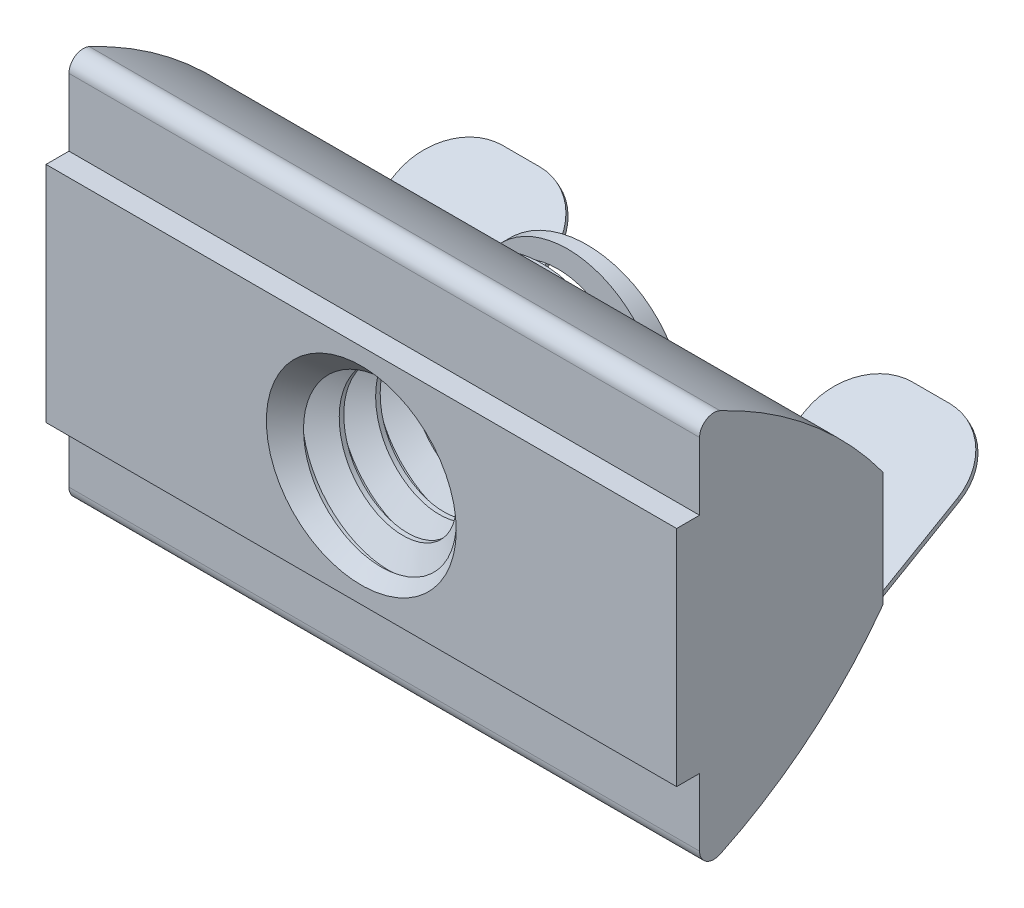
SolidWorks part; units mm, degrees
ref_plane "Front Plane" through (0, 0, 0) normal (0, 0, 1) x (1, 0, 0)
ref_plane "Top Plane" through (0, 0, 0) normal (0, 1, 0) x (1, 0, 0)
ref_plane "Right Plane" through (0, 0, 0) normal (1, 0, 0) x (0, 0, -1)
sketch "Sketch1" plane through (0, 0, 0) normal (0, 0, 1) x (1, 0, 0)
  line L1 (-11, 6.75) -> (11, 6.75)
  line L2 (-11, 6.75) -> (-11, -6.75)
  line L3 (-11, -6.75) -> (11, -6.75)
  line L4 (11, 6.75) -> (11, -6.75)
  circle A0 centre (0, 0) radius 3.175
  point P4 (0, 6.75)
  point P5 (0, 0)
  point P6 (-11, 0)
  point P11 (0, 3.175)
  dimension "Thread Diameter" = 6.35
  dimension "Length" = 22
  dimension "Width" = 13.5
sketch "Sketch2" plane through (0, 0, 0) normal (1, 0, 0) x (0, 0, -1)
  line L0 (-3.6, -3.9) -> (-3.6, 3.9)
  line L1 (-3.6, 3.9) -> (-2.8, 3.9)
  line L4 (-3.6, -3.9) -> (-2.8, -3.9)
  line L8 (-3.6, 0) -> (3.6, 0)
  line L13 (-4.7906, 3.3125) -> (-4.1556, 2.2126)
  line L14 (-4.1556, 2.2126) -> (-3.5206, 3.3125)
  line L15 (-3.5206, 3.3125) -> (-4.7906, 3.3125)
  line L16 (-4.1556, 3.3125) -> (-4.1556, 3.175)
  line L17 (-4.1556, 2.2126) -> (-4.1556, 2.3501)
  line L18 (-4.7113, 3.175) -> (-3.6, 3.175)
  line L19 (-4.7509, 3.2437) -> (-3.5603, 3.2437)
  line L20 (-4.235, 2.3501) -> (-4.0763, 2.3501)
  point P12 (0, 0)
  point P30 (9.2, 0)
  point P39 (-4.1556, 3.175)
  point P42 (-4.1556, 3.2437)
  point P45 (-4.1556, 2.3501)
  dimension "Thickness" = 7.2
  dimension "D2" = 7.8
  dimension "D3" = 0.8
  dimension "Thread Pitch" = 1.27
  dimension "D12" = 0.1588
  dimension "Spring Length" = 12
sketch "Sketch4" plane through (0, 0, 0) normal (1, 0, 0) x (0, 0, -1)
  line L3 (-3.6, -3.9) -> (-2.8, -3.9) construction
  line L4 (-3.6, -3.9) -> (-3.6, 3.9) construction
  line L5 (-3.6, 3.9) -> (-2.8, 3.9) construction
  line L11 (-3.6, -3.9) -> (-2.8, -3.9)
  line L12 (-3.6, -3.9) -> (-3.6, 3.9)
  line L13 (-3.6, 3.9) -> (-2.8, 3.9)
  line L16 (-2.8, 3.9) -> (-2.8, 6.25)
  line L17 (-2.8, -3.9) -> (-2.8, -6.25)
  line L18 (3.6, 2) -> (3.6, -2)
  arc A8 (-2.0859, 6.7019) -> (3.6, 2) centre (-8.5084, -6.8537) cw
  arc A9 (-2.0859, -6.7019) -> (3.6, -2) centre (-8.5084, 6.8537) ccw
  arc A10 (-2.0859, -6.7019) -> (-2.8, -6.25) centre (-2.3, -6.25) cw
  arc A11 (-2.0859, 6.7019) -> (-2.8, 6.25) centre (-2.3, 6.25) ccw
  point P14 (-2.3, 6.75)
  dimension "D1" = 0.5
  dimension "D2" = 15
  dimension "D3" = 4
extrude "Boss-Extrude1" add sketch "Sketch4" against normal up to vertex (11 mm away) and the other way up to vertex (11 mm away) up to point (-11, 6.75, 0) other way up to point (11, 6.75, 0)
sketch "Sketch6" plane through (0, 0, 3.6) normal (0, 0, 1) x (1, 0, 0)
  circle A0 centre (0, 0) radius 3.175 construction
  circle A1 centre (0, 0) radius 3.175
extrude "Cut-Extrude2" cut sketch "Sketch6" against normal through all
sketch "Sketch7" plane through (0, 0, 0) normal (1, 0, 0) x (0, 0, -1)
  line L8 (-2.0859, -6.7588) -> (9.125, -0.2862)
  line L9 (9.125, -0.2862) -> (9.2, -0.4161)
  line L10 (9.2, -0.4161) -> (-2.0109, -6.8887)
  line L11 (-2.0109, -6.8887) -> (-2.0859, -6.7588)
  line L12 (-2.8, -3.9) -> (-2.8, -6.25) construction
  arc A4 (-2.0859, -6.7019) -> (3.6, -2) centre (-8.5084, 6.8537) ccw construction
  arc A5 (-2.0859, -6.7019) -> (3.6, -2) centre (-8.5084, 6.8537) ccw construction
  dimension "D1" = 60
  dimension "D2" = 0.15
extrude "Boss-Extrude4" add sketch "Sketch7" along normal mid plane 19.6 separate body
sketch "Sketch8" plane through (0, -10.5492, 8.351) normal (0, 0.866, 0.5) x (1, 0, 0)
  line L6 (-4.5, 17.7662) -> (-4.5, 20.2662)
  line L7 (-4.5, 20.2662) -> (4.5, 20.2662)
  line L8 (4.5, 20.2662) -> (4.5, 17.7662)
  line L9 (0, 9.3891) -> (0, 15.6245) construction
  line L10 (9.8, 20.2662) -> (-9.8, 20.2662) construction
  arc A1 (-4.5, 17.7662) -> (4.5, 17.7662) centre (0, 17.7662) ccw
  dimension "D2" = 4.5
  dimension "D1" = 2.5
extrude "Cut-Extrude3" cut sketch "Sketch8" along normal through all
fillet "Fillet1" radius 2 4 edges at (-9.8, -0.3512, -9.1625) (-4.5, -0.3512, -9.1625) (4.5, -0.3512, -9.1625) (9.8, -0.3512, -9.1625)
sketch "Sketch17" plane through (0, -10.5492, 8.351) normal (0, 0.866, 0.5) x (1, 0, 0)
  line L0 (0, 9.3891) -> (0, 15.6245) construction
  line L3 (9.8, 7.3209) -> (-9.8, 7.3209) construction
  circle A0 centre (-7.7, 8.3209) radius 0.45
  circle A1 centre (0, 8.3209) radius 0.45
  circle A2 centre (7.7, 8.3209) radius 0.45
  dimension "D2" = 0.9
  dimension "D1" = 15.4
  dimension "D4" = 7.7
  dimension "D3" = 1
extrude "Boss-Extrude3" add sketch "Sketch17" against normal blind 0.075 draft 45
fillet "Fillet4" radius 0.125 6 edges at (7.7, -6.6412, 1.4322) (0, -6.6412, 1.4322) (-7.7, -6.6412, 1.4322) (7.7, -6.6137, 1.5346) (0, -6.6137, 1.5346) (-7.7, -6.6137, 1.5346)
fillet "Fillet5" [suppressed] radius 0.25
sketch "Sketch9" plane through (0, 0, 0) normal (0, 0, 1) x (1, 0, 0)
  line L0 (0, 0) -> (2.2451, -2.2451)
  line L2 (-11, 6.75) -> (11, 6.75) construction
  circle A0 centre (0, 0) radius 3.175 construction
  circle A1 centre (0, 0) radius 3.175
  point P0 (-11, 6.75)
  point P1 (11, 6.75)
  point P3 (-11, -6.75)
  point P13 (2.2451, -2.2451)
  dimension "D1" = 45
sketch "Sketch10" plane through (0, 0, 0) normal (1, 0, 0) x (0, 0, -1)
  point P0 (-3.6, 3.9)
  point P1 (3.6, 3.9)
  point P3 (9.2, 0)
  point P5 (-3.6, -3.9)
sketch "Sketch11" plane through (0, 0, 3.6) normal (0, 0, 1) x (1, 0, 0)
  circle A0 centre (0, 0) radius 3.175
curve "Helix/Spiral1" pitch 1.27 height 8.47 radius 3.175 centre (0, 0, 3.6) axis (0, 0, -1) start towards (0, 1, 0)
sketch "Sketch12" plane through (0, 0, 0) normal (1, 0, 0) x (0, 0, -1)
  line L0 (-4.235, 2.3501) -> (-4.0763, 2.3501) construction
  line L1 (-4.7906, 3.3125) -> (-4.1556, 2.2126) construction
  line L2 (-4.1556, 2.2126) -> (-3.5206, 3.3125) construction
  line L3 (-4.7509, 3.2437) -> (-3.5603, 3.2437) construction
  line L4 (-4.235, 2.3501) -> (-4.0763, 2.3501)
  line L5 (-4.7509, 3.2437) -> (-4.235, 2.3501)
  line L6 (-4.0763, 2.3501) -> (-3.5603, 3.2437)
  line L7 (-4.7509, 3.2437) -> (-3.5603, 3.2437)
sweep "Sweep1" add profiles "Sketch12" path "Helix/Spiral1"
sketch "Sketch13" plane through (0, 0, 3.6) normal (0, 0, 1) x (1, 0, 0)
  circle A0 centre (0, 0) radius 3.3125
extrude "Cut-Extrude4" cut sketch "Sketch13" against normal through all draft 45 and the other way through all
sketch "Sketch14" [suppressed] plane through (11, 0, 0) normal (1, 0, 0) x (0, 0, -1)
  line L6 (-2.8, -3.9) -> (-2.8, -6.25)
  line L7 (-2.8, -4.15) -> (-2.8, -6.25)
  line L8 (3.6, -2) -> (3.6, 2)
  line L9 (3.6, -1.918) -> (3.6, 1.918)
  line L10 (-2.8, 6.25) -> (-2.8, 3.9)
  line L11 (-2.8, 6.25) -> (-2.8, 4.15)
  line L12 (-2.8, 3.9) -> (-3.6, 3.9)
  line L13 (-3.6, 3.9) -> (-3.6, -3.9)
  line L14 (-3.6, -3.9) -> (-2.8, -3.9)
  line L20 (-3.05, 3.9) -> (-3.6, 3.9)
  line L21 (-3.6, 3.9) -> (-3.6, -3.9)
  line L22 (-3.6, -3.9) -> (-3.05, -3.9)
  arc A0 (3.551, -2.0666) -> (3.6, -1.918) centre (3.35, -1.918) ccw construction
  arc A1 (-2.8, -4.15) -> (-3.05, -3.9) centre (-3.05, -4.15) ccw construction
  arc A2 (-3.05, 3.9) -> (-2.8, 4.15) centre (-3.05, 4.15) ccw construction
  arc A3 (3.6, 1.918) -> (3.551, 2.0666) centre (3.35, 1.918) ccw construction
  arc A4 (-2.8, -6.25) -> (-2.0859, -6.7019) centre (-2.3, -6.25) ccw
  arc A5 (-2.8, -6.25) -> (-2.0859, -6.7019) centre (-2.3, -6.25) ccw
  arc A6 (-2.0859, -6.7019) -> (3.6, -2) centre (-8.5084, 6.8537) ccw
  arc A7 (-2.0859, -6.7019) -> (3.551, -2.0666) centre (-8.5084, 6.8537) ccw
  arc A12 (3.6, 2) -> (-2.0859, 6.7019) centre (-8.5084, -6.8537) ccw
  arc A13 (3.551, 2.0666) -> (-2.0859, 6.7019) centre (-8.5084, -6.8537) ccw
  arc A14 (-2.0859, 6.7019) -> (-2.8, 6.25) centre (-2.3, 6.25) ccw
  arc A15 (-2.0859, 6.7019) -> (-2.8, 6.25) centre (-2.3, 6.25) ccw
  arc A16 (3.551, -2.0666) -> (3.6, -1.918) centre (3.35, -1.918) ccw
  arc A17 (-2.8, -4.15) -> (-3.05, -3.9) centre (-3.05, -4.15) ccw
  arc A18 (-3.05, 3.9) -> (-2.8, 4.15) centre (-3.05, 4.15) ccw
  arc A19 (3.6, 1.918) -> (3.551, 2.0666) centre (3.35, 1.918) ccw
  dimension "D1" = 0
extrude "Cut-Extrude5" [suppressed] cut sketch "Sketch14" against normal through all flip side to cut
sketch "Sketch16" plane through (0, 0, 0) normal (1, 0, 0) x (0, 0, -1)
  line L0 (3.6, 0) -> (3.6, 4.1287)
  line L1 (3.6, 3.175) -> (2.6463, 3.175) construction
  line L2 (3.6, 4.1287) -> (0, 0.5287)
  line L3 (0, 0.5287) -> (0, 0)
  line L4 (0, 0) -> (3.6, 0)
  line L5 (-4.7113, 3.175) -> (-3.6, 3.175) construction
  arc A1 (3.6, 2) -> (-2.0859, 6.7019) centre (-8.5084, -6.8537) ccw construction
  dimension "D1" = 45
revolve "Cut-Revolve1" cut sketch "Sketch16" angle 360 about L4
equation "\"D12@Sketch2\"=\"Thread Pitch@Sketch2\"/8"
equation "\"D3@Helix/Spiral1\"=\"Thickness@Sketch2\"+\"Thread Pitch@Sketch2\""
equation "\"D4@Helix/Spiral1\"=\"Thread Pitch@Sketch2\""
equation "\"D4@Sketch17\"=\"D1@Sketch17\"/2"
equation "\"D1@Sketch17\"=\"Length@Sketch1\"*.7"
